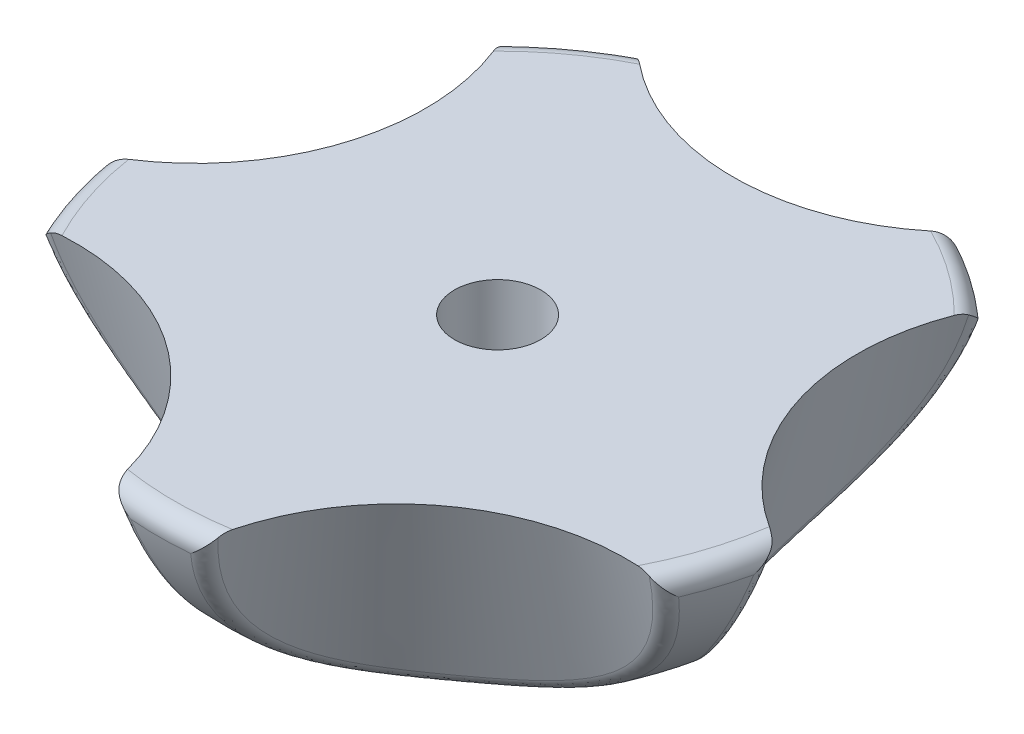
SolidWorks part; units mm, degrees
ref_plane "Plan de face" through (0, 0, 0) normal (0, 0, 1) x (1, 0, 0)
ref_plane "Plan de dessus" through (0, 0, 0) normal (0, 1, 0) x (1, 0, 0)
ref_plane "Plan de droite" through (0, 0, 0) normal (1, 0, 0) x (0, 0, -1)
sketch "Esquisse1" plane through (0, 0, 0) normal (0, 1, 0) x (1, 0, 0)
  circle A0 centre (0, 0) radius 2.5
  circle A1 centre (0, 0) radius 20
  dimension "D1" = 5
  dimension "D2" = 40
extrude "Boss.-Extru.1" add sketch "Esquisse1" along normal blind 12
fillet "Congé7" radius 15 1 edges at (0, 0, 20)
sketch "Esquisse2" plane through (0, 12, 0) normal (0, 1, 0) x (1, 0, 0)
  line L0 (0, 0) -> (0, 17.1605) construction
  arc A0 (-9.4826, 17.6091) -> (9.3573, 17.676) centre (-0.0961, 27.0625) ccw
  circle A1 centre (0, 0) radius 20 construction
  arc A2 (-9.4826, 17.6091) -> (9.3573, 17.676) centre (0, 0) cw
  dimension "D2" = 18.84
extrude "Enlèv. mat.-Extru.1" cut sketch "Esquisse2" against normal through all draft 15 draft outward yes
ref_axis "Axe1" through (0, -0.4, 0) along (0, 1, 0)
pattern_circular "Répétition circulaire1" count 5 over 360 about axis through (0, -0.4, 0) along (0, 1, 0) of "Enlèv. mat.-Extru.1"
sketch "Esquisse3" plane through (0, 0, 0) normal (0, -1, 0) x (1, 0, 0)
  circle A1 centre (0, 0) radius 5.3031
  circle A2 centre (0, 0) radius 5.3031
  dimension "D1" = 0
extrude "Enlèv. mat.-Extru.2" cut sketch "Esquisse3" against normal blind 2 draft 45
fillet "Congé9" radius 1 11 edges at (0, 0, -5.3031) (-18.9991, 12, 6.2478) (-7.0525, 1.0722, 8.2745) (0.071, 12, 19.9999) (5.6902, 1.0722, 9.2643) (19.0429, 12, 6.1128) (10.5693, 1.0722, -2.5489) (11.6982, 12, -16.222) (0.842, 1.0722, -10.8396) (-11.8131, 12, -16.1385) (-10.0489, 1.0722, -4.1504)
